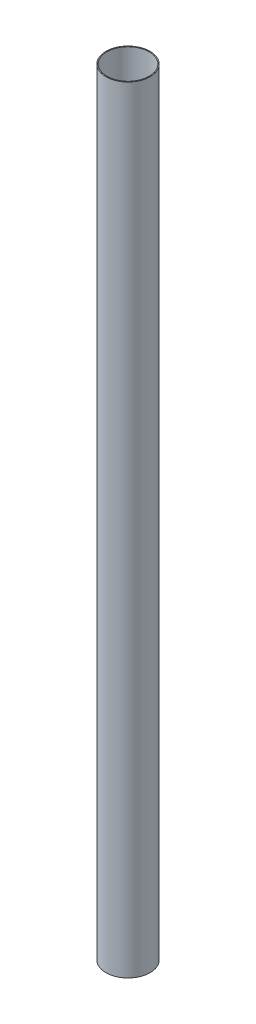
SolidWorks part; units mm, degrees
material "Stop 1060"
ref_plane "Płaszczyzna przednia" through (0, 0, 0) normal (0, 0, 1) x (1, 0, 0)
ref_plane "Płaszczyzna górna" through (0, 0, 0) normal (0, 1, 0) x (1, 0, 0)
ref_plane "Płaszczyzna prawa" through (0, 0, 0) normal (1, 0, 0) x (0, 0, -1)
sketch "Szkic1" plane through (0, 0, 0) normal (0, 1, 0) x (1, 0, 0)
  circle A0 centre (0, 0) radius 24.3
  circle A1 centre (0, 0) radius 25.3
  dimension "D1" = 48.6
  dimension "D2" = 50.6
extrude "Dodanie-wyciągnięcie1" add sketch "Szkic1" along normal blind 890
